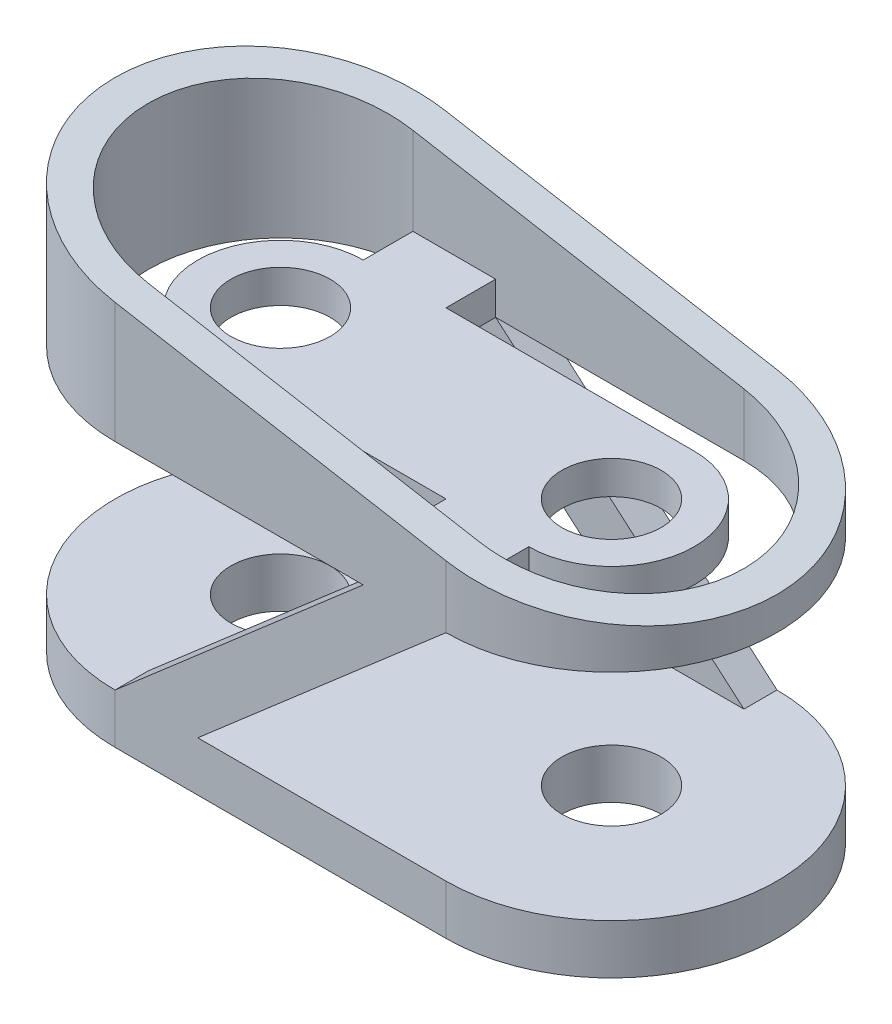
SolidWorks part; units mm, degrees
material "2014 Alloy"
ref_plane "Front Plane" through (0, 0, 0) normal (0, 0, 1) x (1, 0, 0)
ref_plane "Top Plane" through (0, 0, 0) normal (0, 1, 0) x (1, 0, 0)
ref_plane "Right Plane" through (0, 0, 0) normal (1, 0, 0) x (0, 0, -1)
sketch "Sketch1" plane through (0, 0, 0) normal (0, 1, 0) x (1, 0, 0)
  line L0 (-50, 0) -> (50, 0) construction
  line L1 (-50, 50) -> (50, 50)
  line L2 (-50, -50) -> (50, -50)
  arc A0 (-50, 50) -> (-50, -50) centre (-50, 0) ccw
  arc A1 (50, -50) -> (50, 50) centre (50, 0) ccw
  dimension "D2" = 100
  dimension "D1" = 100
extrude "Boss-Extrude1" add sketch "Sketch1" along normal blind 15
sketch "Sketch6" plane through (0, 15, 0) normal (0, 1, 0) x (1, 0, 0)
  circle A0 centre (50, 0) radius 15
  circle A1 centre (-50, 0) radius 15
  dimension "D2" = 30
extrude "Cut-Extrude2" cut sketch "Sketch6" against normal through all
extrude "Boss-Extrude2" add sketch "Sketch1<2>" along normal blind 10 from offset 80 separate body
sketch "Sketch1<2>" plane through (0, 0, 0) normal (0, 1, 0) x (1, 0, 0) same geometry as "Sketch1"
sketch "Sketch3" plane through (0, 0, 50) normal (0, 0, 1) x (1, 0, 0)
  line L0 (-50, 15) -> (25, 80)
  line L1 (-50, 15) -> (50, 15) construction
  line L2 (-50, 80) -> (50, 80) construction
  line L5 (-25, 15) -> (50, 80)
  line L6 (-50, 15) -> (-25, 15)
  line L7 (25, 80) -> (50, 80)
  dimension "D1" = 50
  dimension "D2" = 75
  dimension "D3" = 75
extrude "Boss-Extrude3" add sketch "Sketch3" against normal blind 10
sketch "Sketch4" plane through (0, 0, -50) normal (0, 0, -1) x (-1, 0, 0)
  line L0 (-50, 15) -> (25, 80)
  line L1 (-50, 80) -> (50, 80) construction
  line L2 (25, 80) -> (50, 80)
  line L3 (50, 80) -> (-25, 15)
  line L4 (-50, 15) -> (50, 15) construction
  line L5 (-50, 15) -> (-25, 15)
  dimension "D1" = 50
  dimension "D2" = 75
  dimension "D3" = 75
  dimension "D4" = 50
extrude "Boss-Extrude4" add sketch "Sketch4" against normal blind 10
sketch "Sketch7" plane through (0, 90, 0) normal (0, 1, 0) x (1, 0, 0)
  line L0 (-50, 0) -> (50, 0) construction
  line L1 (-50, -25) -> (25, -25)
  line L2 (50, 25) -> (-25, 25)
  line L3 (50, -25) -> (50, -50)
  line L4 (50, -50) -> (25, -50)
  line L5 (-50, -50) -> (50, -50) construction
  line L6 (25, -50) -> (25, -25)
  line L8 (-50, 25) -> (-50, 50)
  line L9 (-25, 25) -> (-25, 50)
  line L10 (50, 50) -> (-50, 50) construction
  line L11 (-25, 50) -> (-50, 50)
  arc A0 (-50, 25) -> (-50, -25) centre (-50, 0) ccw
  arc A1 (50, -25) -> (50, 25) centre (50, 0) ccw
  arc A2 (-50, 50) -> (-50, -50) centre (-50, 0) ccw construction
  point P26 (-100, 0)
  dimension "D2" = 50
  dimension "D1" = 100
  dimension "D3" = 25
  dimension "D4" = 75
sketch "Sketch8" plane through (0, 90, 0) normal (0, 1, 0) x (1, 0, 0)
  line L2 (-50, -50) -> (50, -50)
  line L3 (50, 50) -> (-50, 50)
  line L4 (-50, -50) -> (50, -50)
  line L5 (50, 50) -> (-50, 50)
  arc A2 (-50, 50) -> (-50, -50) centre (-50, 0) ccw
  arc A3 (50, -50) -> (50, 50) centre (50, 0) ccw
  arc A4 (-50, 50) -> (-50, -50) centre (-50, 0) ccw
  arc A5 (50, -50) -> (50, 50) centre (50, 0) ccw
  point P0 (-50, -50)
  dimension "D1" = 0
extrude "Cut-Extrude3" cut sketch "Sketch7" against normal blind 10 flip side to cut contours A0 L1 L6 L4 L3 A1 L2 L9 L11 L8
sketch "Sketch9" plane through (0, 90, 0) normal (0, 1, 0) x (1, 0, 0)
  circle A0 centre (-50, 0) radius 15
  circle A1 centre (50, 0) radius 15
  dimension "D1" = 30
extrude "Cut-Extrude4" cut sketch "Sketch9" against normal blind 10
sketch "Sketch10" plane through (0, 90, 0) normal (0, 1, 0) x (1, 0, 0)
  line L0 (-50, -50) -> (50, -50) construction
  line L1 (50, 50) -> (-50, 50) construction
  line L2 (25, -50) -> (50, -50) construction
  line L3 (-50, -50) -> (50, -50)
  line L4 (25, -50) -> (50, -50)
  line L5 (50, 50) -> (-50, 50)
  line L6 (-50, -40) -> (37.5, -40)
  line L7 (37.5, -40) -> (37.5, -40)
  line L8 (50, 25) -> (-25, 25)
  line L9 (-25, 25) -> (-25, 50)
  line L10 (-25, 50) -> (-50, 50)
  line L11 (-50, 50) -> (-50, 25)
  line L12 (-50, -25) -> (25, -25)
  line L13 (25, -25) -> (25, -50)
  line L14 (25, -50) -> (50, -50)
  line L15 (50, -50) -> (50, -25)
  line L18 (-25, 50) -> (-50, 50)
  line L22 (25, -50) -> (50, -50)
  line L24 (37.5, -40) -> (50, -40)
  line L25 (50, 40) -> (-50, 40)
  line L26 (-25, 40) -> (-50, 40)
  arc A0 (-50, 50) -> (-50, -50) centre (-50, 0) ccw construction
  arc A1 (50, -50) -> (50, 50) centre (50, 0) ccw construction
  arc A2 (-50, 25) -> (-50, -25) centre (-50, 0) ccw
  arc A3 (50, -25) -> (50, 25) centre (50, 0) ccw
  arc A6 (50, -50) -> (50, 50) centre (50, 0) ccw
  arc A7 (-50, 50) -> (-50, -50) centre (-50, 0) ccw
  arc A8 (50, -40) -> (50, 40) centre (50, 0) ccw
  arc A9 (-50, 40) -> (-50, -40) centre (-50, 0) ccw
  line M14 (-25, 25) -> (-25, 50)
  line M15 (-25, 50) -> (-50, 50)
  line M16 (-50, 50) -> (-50, 25)
  line M19 (25, -25) -> (25, -50)
  line M20 (25, -50) -> (50, -50)
  line M21 (50, -50) -> (50, -25)
  dimension "D1" = 0
  dimension "D2" = 10
sketch "Sketch11" plane through (0, 0, 0) normal (0, 0, 1) x (1, 0, 0)
  line L0 (100, 90) -> (-119.5239, 112.063) construction
  line L1 (100, 90) -> (50, 90) construction
  line L2 (100, 90) -> (-100, 90) construction
  line L3 (-50, 90) -> (-100, 90) construction
  point P10 (0, 90)
  dimension "D1" = 10
extrude "Boss-Extrude5" add sketch "Sketch10" along normal blind 40 and the other way blind 10 contours A9 A7 L3 L6 M16 M19 | A8 A6 L5 L25 M21 M14 | L25 M14 M15 M16 | L24 L6 M19 M20 M21 region at (-98.3992, 90, 0) region at (37.5, 90, 45) region at (-37.5, 90, -45) region at (51.6008, 90, 45)
sketch "Sketch13" plane through (0, 90, 0) normal (0, 1, 0) x (1, 0, 0)
  line L0 (50, 0) -> (100, 0) construction
  arc A0 (50, -50) -> (50, 50) centre (50, 0) ccw construction
sketch "Sketch14" plane through (0, 0, 0) normal (0, 0, 1) x (1, 0, 0)
  line L0 (100, 90) -> (-120.8362, 128.9394)
  line L1 (50, 90) -> (-50, 90) construction
  dimension "D1" = 10
extrude "Cut-Extrude6" cut sketch "Sketch14" against normal through all and the other way through all flip side to cut
